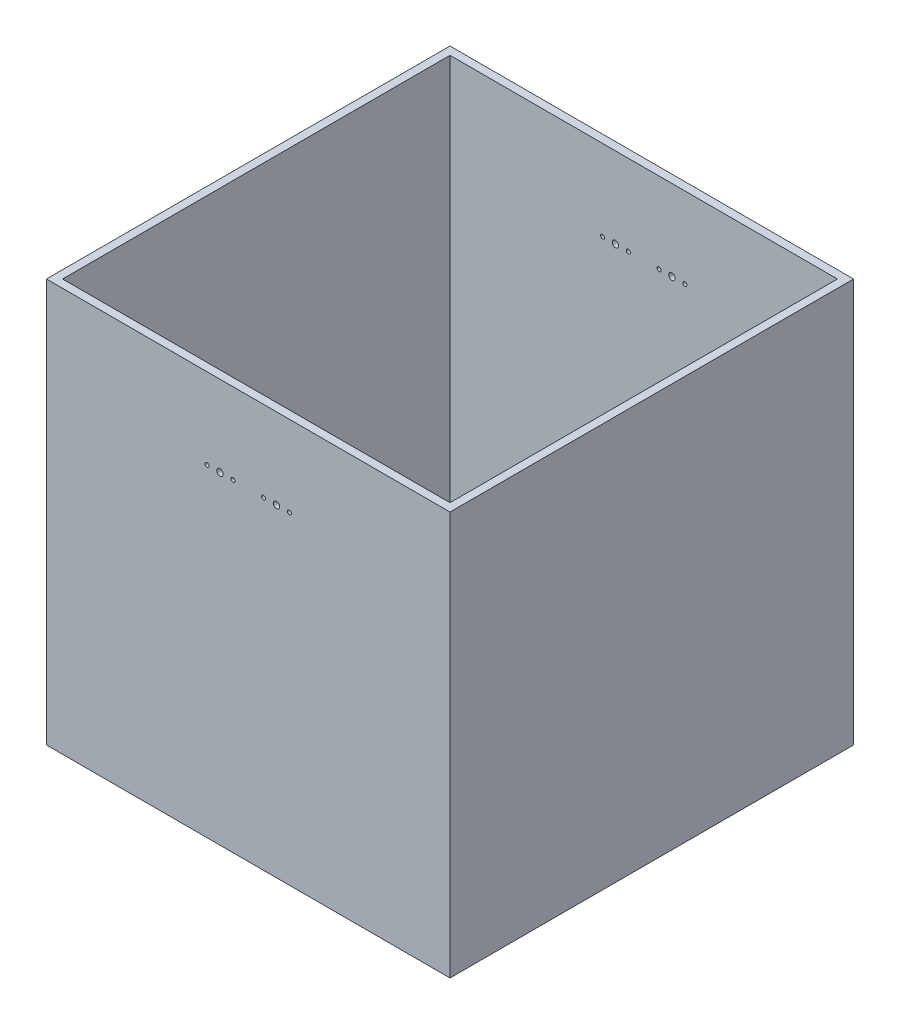
SolidWorks part; units mm, degrees
material "Acrylic (Medium-high impact)"
ref_plane "Front Plane" through (0, 0, 0) normal (0, 0, 1) x (1, 0, 0)
ref_plane "Top Plane" through (0, 0, 0) normal (0, 1, 0) x (1, 0, 0)
ref_plane "Right Plane" through (0, 0, 0) normal (1, 0, 0) x (0, 0, -1)
sketch "Sketch1" plane through (0, 0, 0) normal (0, 1, 0) x (1, 0, 0)
  line L0 (-240, 240) -> (240, 240)
  line L1 (-250, 250) -> (250, 250)
  line L2 (-250, 250) -> (-250, -250)
  line L3 (-250, -250) -> (250, -250)
  line L4 (250, 250) -> (250, -250)
  line L5 (-250, 250) -> (250, -250) construction
  line L6 (-250, -250) -> (250, 250) construction
  line L7 (240, 240) -> (240, -240)
  line L8 (-240, -240) -> (240, -240)
  line L9 (-240, 240) -> (-240, -240)
  circle A0 centre (0, 0) radius 250 construction
  point P0 (0, 0)
  dimension "D1" = 500
  dimension "D2" = 500
  dimension "D3" = 10
extrude "Boss-Extrude1" add sketch "Sketch1" along normal blind 500
sketch "Sketch2" plane through (0, 500, 0) normal (0, 1, 0) x (1, 0, 0)
  line L0 (-252.1839, 0.2203) -> (250, 0.2203) construction
  line L1 (-252.1839, -249.5595) -> (250, -249.5595) construction
  line L2 (-252.1839, -249.5595) -> (-252.1839, 250) construction
  line L3 (-252.1839, 250) -> (250, 250) construction
  line L4 (250, -249.5595) -> (250, 250) construction
  line L5 (-252.1839, -249.5595) -> (250, 250) construction
  line L6 (-252.1839, 250) -> (250, -249.5595) construction
  point P0 (-1.0919, 0.2203)
sketch "Sketch4" plane through (0, 0, -250) normal (0, 0, -1) x (-1, 0, 0)
  line L0 (-35, 400) -> (35, 400) construction
  line L1 (0, 0) -> (0, 400) construction
  line L2 (-250, 0) -> (250, 0) construction
  line L3 (-35, 400) -> (-35, 391.4181) construction
  circle A0 centre (35, 400) radius 4
  circle A1 centre (-35, 400) radius 4
  circle A2 centre (-19, 400) radius 2.5
  circle A3 centre (-51, 400) radius 2.5
  circle A4 centre (19, 400) radius 2.5
  circle A5 centre (51, 400) radius 2.5
  point P6 (0, 400)
  dimension "D2" = 8
  dimension "D3" = 5
  dimension "D1" = 35
  dimension "D4" = 16
  dimension "D5" = 400
extrude "Cut-Extrude2" cut sketch "Sketch4" against normal through all both
